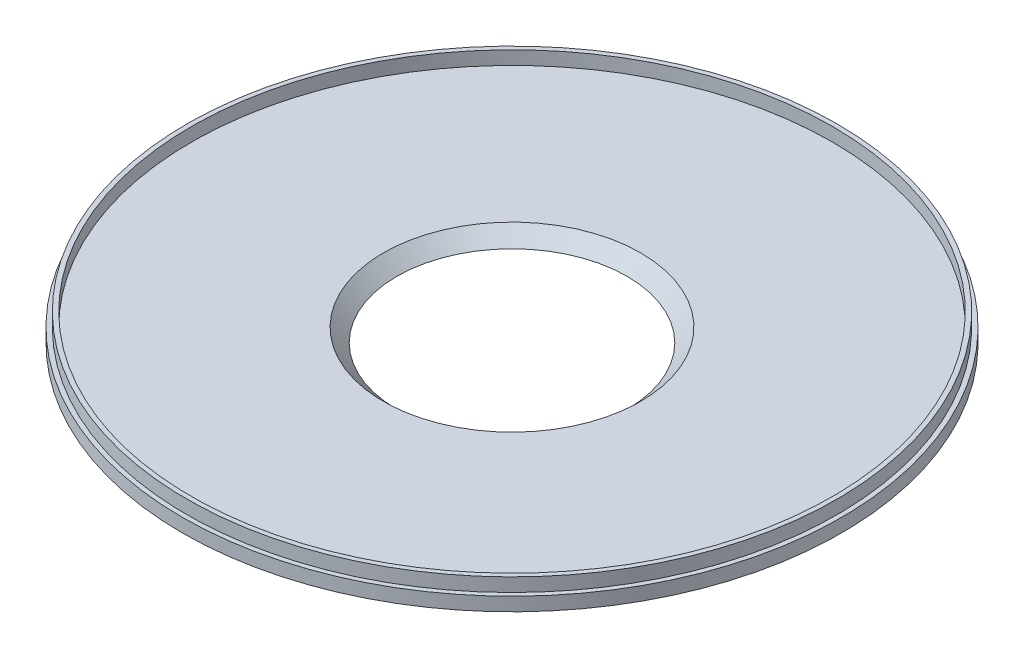
SolidWorks part; units mm, degrees
material "Silica Phenolic"
ref_plane "Piano frontale" through (0, 0, 0) normal (0, 0, 1) x (1, 0, 0)
ref_plane "Piano superiore" through (0, 0, 0) normal (0, 1, 0) x (1, 0, 0)
ref_plane "Piano destro" through (0, 0, 0) normal (1, 0, 0) x (0, 0, -1)
sketch "Schizzo1" plane through (0, 0, 0) normal (0, 0, 1) x (1, 0, 0)
  line L0 (-25.5, 0) -> (-25.5, 3)
  line L1 (-25.5, 3) -> (-71, 3)
  line L2 (-71, 3) -> (-71, 6)
  line L3 (-71, 6) -> (-72, 6)
  line L4 (-72, 6) -> (-72, 3)
  line L5 (-72, 3) -> (-73, 3)
  line L6 (-73, 3) -> (-73, 0)
  line L7 (-73, 0) -> (-25.5, 0)
  line L8 (0, 0) -> (0, 18.8486) construction
  dimension "D1" = 51
  dimension "D2" = 146
  dimension "D3" = 1
  dimension "D4" = 3
  dimension "D5" = 1
  dimension "D6" = 3
revolve "Rivoluzione1" add sketch "Schizzo1" angle 360 about L8
chamfer "Smusso1" distance 3 angle 45 1 edges at (0, 3, -25.5)
